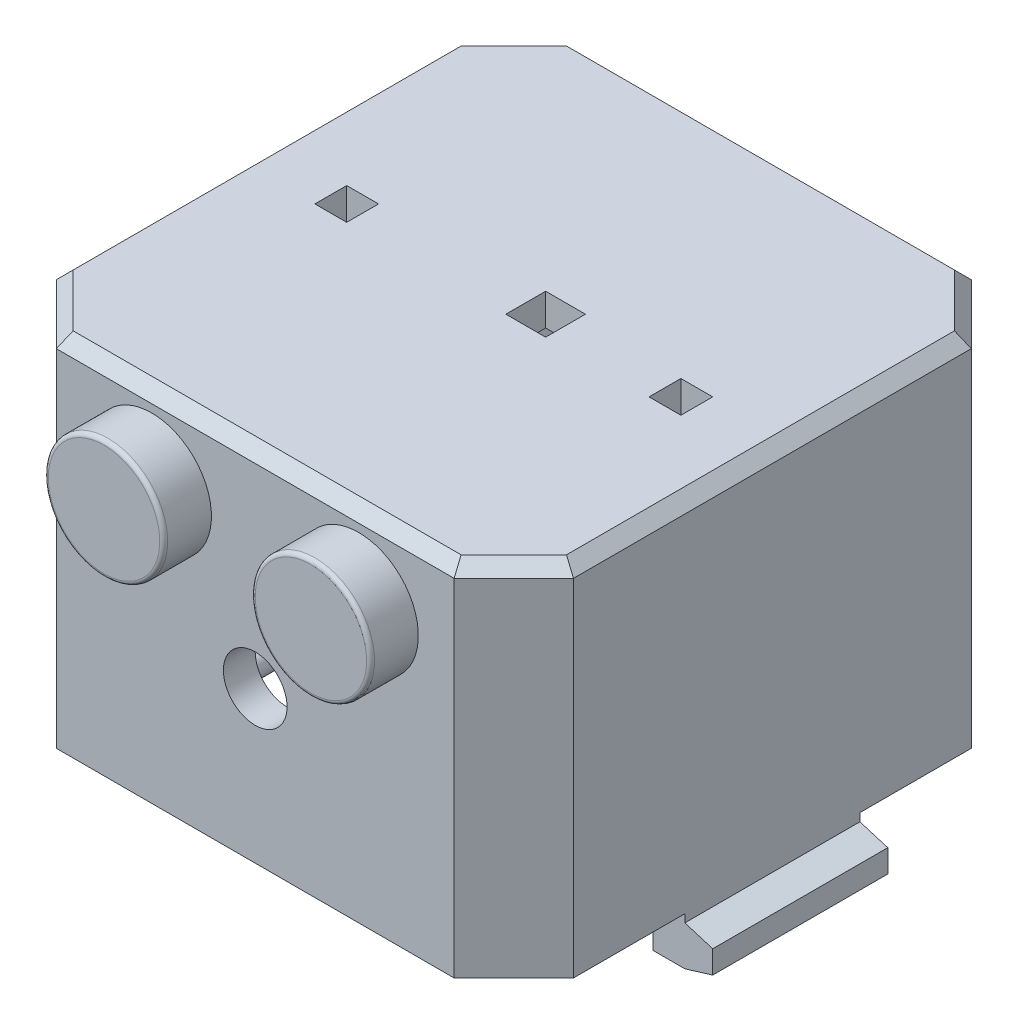
SolidWorks part; units mm, degrees
ref_plane "Alzado" through (0, 0, 0) normal (0, 0, 1) x (1, 0, 0)
ref_plane "Planta" through (0, 0, 0) normal (0, 1, 0) x (1, 0, 0)
ref_plane "Vista lateral" through (0, 0, 0) normal (1, 0, 0) x (0, 0, -1)
sketch "Croquis1" plane through (0, 0, 0) normal (0, 1, 0) x (1, 0, 0)
  line L1 (-25, -32.5) -> (25, -32.5)
  line L3 (-25, 32.5) -> (25, 32.5)
  line L5 (-25, -32.5) -> (25, 32.5) construction
  line L6 (-25, 32.5) -> (25, -32.5) construction
  line L10 (32.5, 25) -> (32.5, -25)
  line L11 (25, -32.5) -> (32.5, -25)
  line L12 (32.5, 25) -> (25, 32.5)
  line L13 (-32.5, 25) -> (-32.5, -25)
  line L14 (-32.5, -25) -> (-25, -32.5)
  line L15 (-32.5, 25) -> (-25, 32.5)
  point P0 (0, 0)
  point P10 (0, 32.5)
  dimension "D1" = 65
  dimension "D2" = 65
  dimension "D3" = 50
  dimension "D4" = 50
  dimension "D5" = 25
  dimension "D6" = 25
extrude "Saliente-Extruir1" add sketch "Croquis1" along normal blind 45
shell "Vaciado2" thickness 4 removed face at (0, 0, 0)
chamfer "Chaflán3" distance 1.5 angle 45 8 edges at (0, 45, -32.5) (32.5, 45, 0) (0, 45, 32.5) (-32.5, 45, 0) (-28.75, 45, 28.75) (28.75, 45, 28.75) (28.75, 45, -28.75) (-28.75, 45, -28.75)
sketch "Croquis2" plane through (0, 0, 32.5) normal (0, 0, 1) x (1, 0, 0)
  line L0 (0, 0) -> (0, 6.916) construction
  circle A0 centre (13, 35) radius 7.5
  circle A1 centre (-13, 35) radius 7.5
  dimension "D1" = 15
  dimension "D2" = 13
  dimension "D3" = 35
extrude "Saliente-Extruir2" add sketch "Croquis2" along normal blind 6
sketch "Croquis4" plane through (0, 0, 28.5) normal (0, 0, -1) x (-1, 0, 0)
  line L0 (0, 0) -> (0, 4.7403) construction
  line L1 (0, 0) -> (0, 6.916) construction
  circle A0 centre (-13, 35) radius 5
  circle A1 centre (13, 35) radius 5
  dimension "D1" = 10
extrude "Cortar-Extruir2" cut sketch "Croquis4" against normal blind 8
fillet "Redondeo1" radius 0.5 2 edges at (-20.5, 35, 38.5) (20.5, 35, 38.5)
sketch "Croquis5" plane through (0, 0, 32.5) normal (0, 0, 1) x (1, 0, 0)
  circle A0 centre (0, 19) radius 4
  dimension "D2" = 8
  dimension "D1" = 19
extrude "Cortar-Extruir3" cut sketch "Croquis5" against normal blind 10
sketch "Croquis13" plane through (0, 0, 36.5) normal (0, 0, -1) x (-1, 0, 0)
  circle A0 centre (-13, 35) radius 2.6
  circle A1 centre (13, 35) radius 2.6
  circle A2 centre (13, 35) radius 5
  circle A3 centre (-13, 35) radius 5
  dimension "D1" = 5.2
  dimension "D2" = 5.2
extrude "Saliente-Extruir8" add sketch "Croquis13" along normal blind 8
sketch "Croquis7" plane through (0, 0, 28.5) normal (0, 0, -1) x (-1, 0, 0)
  line L0 (23.3431, 0) -> (-23.3431, 0) construction
  line L1 (-14.08, 8) -> (-9.08, 8)
  line L2 (-14.08, 8) -> (-14.08, 13)
  line L3 (-14.08, 13) -> (-9.08, 13)
  line L4 (-9.08, 8) -> (-9.08, 13)
  line L5 (-14.08, 8) -> (-9.08, 13) construction
  line L6 (-14.08, 13) -> (-9.08, 8) construction
  line L8 (-14.08, 25.5) -> (-9.08, 25.5)
  line L9 (-14.08, 25.5) -> (-14.08, 30.5)
  line L10 (-14.08, 30.5) -> (-9.08, 30.5)
  line L11 (-9.08, 25.5) -> (-9.08, 30.5)
  line L12 (-14.08, 25.5) -> (-9.08, 30.5) construction
  line L13 (-14.08, 30.5) -> (-9.08, 25.5) construction
  line L14 (13.93, 13) -> (8.93, 8) construction
  line L15 (13.93, 8) -> (8.93, 13) construction
  line L16 (8.93, 8) -> (8.93, 13)
  line L17 (13.93, 13) -> (8.93, 13)
  line L18 (13.93, 8) -> (13.93, 13)
  line L19 (13.93, 8) -> (8.93, 8)
  line L20 (13.93, 30.5) -> (8.93, 25.5) construction
  line L21 (13.93, 25.5) -> (8.93, 30.5) construction
  line L22 (8.93, 25.5) -> (8.93, 30.5)
  line L23 (13.93, 30.5) -> (8.93, 30.5)
  line L24 (13.93, 25.5) -> (13.93, 30.5)
  line L25 (13.93, 25.5) -> (8.93, 25.5)
  point P0 (-11.58, 10.5)
  point P8 (-11.58, 28)
  point P13 (0, 0)
  point P15 (11.43, 10.5)
  point P16 (11.43, 28)
  point P20 (11.43, 10.5)
  point P25 (11.43, 28)
  point P26 (-11.58, 28)
  point P27 (11.43, 28)
  point P28 (11.43, 10.5)
  point P29 (-11.58, 10.5)
  dimension "D1" = 10.5
  dimension "D2" = 5
  dimension "D3" = 5
  dimension "D4" = 11.58
  dimension "D5" = 5
  dimension "D6" = 5
  dimension "D7" = 28
  dimension "D8" = 23.01
  dimension "D9" = 23.01
  dimension "D10" = 5
  dimension "D11" = 5
  dimension "D12" = 5
  dimension "D13" = 5
  dimension "D14" = 10.5
  dimension "D15" = 28
extrude "Saliente-Extruir3" add sketch "Croquis7" along normal blind 1
sketch "Croquis8" plane through (0, 0, 27.5) normal (0, 0, -1) x (-1, 0, 0)
  line L0 (0, 0) -> (0, 4.8013) construction
  line L1 (23.3431, 0) -> (-23.3431, 0) construction
  circle A0 centre (-11.505, 10.4893) radius 1.6
  circle A1 centre (-11.505, 27.9763) radius 1.6
  circle A2 centre (11.505, 10.4893) radius 1.6
  circle A3 centre (11.505, 27.9763) radius 1.6
  dimension "D1" = 3.2
  dimension "D2" = 3.2
  dimension "D5" = 3.2
  dimension "D3" = 23.01
  dimension "D4" = 23.01
sketch "Croquis12" plane through (0, 41, 0) normal (0, -1, 0) x (1, 0, 0)
  line L0 (0, 0) -> (-5.199, 0) construction
  line L1 (-21.9, -8.93) -> (21.9, -8.93) construction
  line L2 (-21.9, -8.93) -> (-21.9, 8.93) construction
  line L3 (-21.9, 8.93) -> (21.9, 8.93) construction
  line L4 (21.9, -8.93) -> (21.9, 8.93) construction
  line L5 (-21.9, -8.93) -> (21.9, 8.93) construction
  line L6 (-21.9, 8.93) -> (21.9, -8.93) construction
  line L7 (0, 0) -> (0, 4.1573) construction
  circle A0 centre (-20.65, 7.68) radius 0.8
  circle A1 centre (-20.65, 7.68) radius 1.15
  circle A2 centre (-20.65, -7.68) radius 1.15
  circle A3 centre (-20.65, -7.68) radius 0.8
  circle A4 centre (20.65, 7.68) radius 1.15
  circle A5 centre (20.65, 7.68) radius 0.8
  circle A6 centre (20.65, -7.68) radius 1.15
  circle A7 centre (20.65, -7.68) radius 0.8
  point P0 (0, 0)
  dimension "D6" = 1.6
  dimension "D4" = 2.3
  dimension "D1" = 43.8
  dimension "D2" = 17.86
  dimension "D3" = 1.25
  dimension "D7" = 1.25
extrude "Saliente-Extruir7" add sketch "Croquis12" along normal blind 6
sketch "Croquis14" plane through (0, 41, 0) normal (0, -1, 0) x (1, 0, 0)
  line L1 (-22.15, 6.43) -> (-19.15, 6.43)
  line L2 (-22.15, 6.43) -> (-22.15, 8.93)
  line L3 (-22.15, 8.93) -> (-19.15, 8.93)
  line L4 (-19.15, 6.43) -> (-19.15, 8.93)
  line L5 (-22.15, 6.43) -> (-19.15, 8.93) construction
  line L6 (-22.15, 8.93) -> (-19.15, 6.43) construction
  line L7 (-22.15, -8.93) -> (-19.15, -8.93)
  line L8 (-22.15, -8.93) -> (-22.15, -6.43)
  line L9 (-22.15, -6.43) -> (-19.15, -6.43)
  line L10 (-19.15, -8.93) -> (-19.15, -6.43)
  line L11 (-22.15, -8.93) -> (-19.15, -6.43) construction
  line L12 (-22.15, -6.43) -> (-19.15, -8.93) construction
  line L13 (19.15, 6.43) -> (22.15, 6.43)
  line L14 (19.15, 6.43) -> (19.15, 8.93)
  line L15 (19.15, 8.93) -> (22.15, 8.93)
  line L16 (22.15, 6.43) -> (22.15, 8.93)
  line L17 (19.15, 6.43) -> (22.15, 8.93) construction
  line L18 (19.15, 8.93) -> (22.15, 6.43) construction
  line L19 (19.15, -8.93) -> (22.15, -8.93)
  line L20 (19.15, -8.93) -> (19.15, -6.43)
  line L21 (19.15, -6.43) -> (22.15, -6.43)
  line L22 (22.15, -8.93) -> (22.15, -6.43)
  line L23 (19.15, -8.93) -> (22.15, -6.43) construction
  line L24 (19.15, -6.43) -> (22.15, -8.93) construction
  point P0 (-20.65, 7.68)
  point P6 (-20.65, -7.68)
  point P12 (20.65, 7.68)
  point P18 (20.65, -7.68)
  dimension "D1" = 3
  dimension "D2" = 2.5
  dimension "D3" = 3
  dimension "D4" = 2.5
  dimension "D5" = 3
  dimension "D6" = 2.5
  dimension "D7" = 3
  dimension "D8" = 2.5
extrude "Saliente-Extruir9" add sketch "Croquis14" along normal blind 5
sketch "Croquis15" plane through (-32.5, 0, 0) normal (-1, 0, 0) x (0, 0, 1)
  line L1 (-6, 40.5) -> (6, 40.5)
  line L2 (-6, 40.5) -> (-6, 32.5)
  line L3 (-6, 32.5) -> (6, 32.5)
  line L4 (6, 40.5) -> (6, 32.5)
  dimension "D1" = 8
  dimension "D2" = 12
  dimension "D3" = 3
  dimension "D4" = 19
extrude "Cortar-Extruir6" cut sketch "Croquis15" against normal blind 7
sketch "Croquis16" plane through (0, 0, -28.5) normal (0, 0, 1) x (1, 0, 0)
  line L2 (18.95, 6.05) -> (6.55, 6.05)
  line L3 (18.95, 6.05) -> (18.95, 18.45)
  line L4 (18.95, 18.45) -> (6.55, 18.45)
  line L5 (6.55, 6.05) -> (6.55, 18.45)
  line L6 (5.5, 5) -> (20, 5)
  line L7 (5.5, 5) -> (5.5, 19.5)
  line L8 (5.5, 19.5) -> (20, 19.5)
  line L9 (20, 5) -> (20, 19.5)
  line L10 (5.5, 5) -> (20, 19.5) construction
  line L11 (5.5, 19.5) -> (20, 5) construction
  line L12 (18.95, 6.05) -> (6.55, 18.45) construction
  line L13 (18.95, 18.45) -> (6.55, 6.05) construction
  point P0 (12.75, 12.25)
  point P4 (12.75, 12.25)
  dimension "D1" = 12.4
  dimension "D2" = 12.4
  dimension "D3" = 5
  dimension "D4" = 5
  dimension "D5" = 14.5
  dimension "D6" = 14.5
extrude "Saliente-Extruir10" add sketch "Croquis16" along normal blind 3
sketch "Croquis17" plane through (0, 0, -28.5) normal (0, 0, 1) x (1, 0, 0)
  circle A0 centre (12.75, 12.25) radius 5.5
  point P4 (12.75, 12.25)
  dimension "D1" = 11
extrude "Cortar-Extruir7" cut sketch "Croquis17" against normal through all
sketch "Croquis18" plane through (0, 0, 0) normal (0, -1, 0) x (1, 0, 0)
  line L1 (-32.5, 11) -> (-28.5, 11)
  line L2 (-32.5, 11) -> (-32.5, -11)
  line L3 (-32.5, -11) -> (-28.5, -11)
  line L4 (-28.5, 11) -> (-28.5, -11)
  line L5 (-32.5, -25) -> (-32.5, 25) construction
  line L6 (0, 0) -> (0, 8.739) construction
  line L7 (28.5, 11) -> (28.5, -11)
  line L8 (32.5, -11) -> (28.5, -11)
  line L9 (32.5, 11) -> (32.5, -11)
  line L10 (32.5, 11) -> (28.5, 11)
  point P4 (-28.5, 0)
  dimension "D1" = 4
  dimension "D2" = 22
extrude "Saliente-Extruir11" add sketch "Croquis18" along normal blind 6
sketch "Croquis19" plane through (0, 0, 11) normal (0, 0, 1) x (1, 0, 0)
  line L0 (-32.5, -3.5) -> (-34.5, -3.5) construction
  line L1 (36, -2.0667) -> (36, -4.9333)
  line L2 (-34.5, -2.0568) -> (-32.5, -1)
  line L3 (-32.5, -6) -> (-32.5, 0)
  line L4 (-32.5, -6) -> (-32.5, -1)
  line L5 (-32.5, -6) -> (-34.5, -4.9432)
  line L6 (0, 0) -> (0, 6.3616) construction
  line L7 (-25, 0) -> (25, 0) construction
  line L8 (32.5, -3.5) -> (36, -3.5) construction
  line L9 (32.5, -6) -> (36, -4.9333)
  line L10 (32.5, -6) -> (32.5, -1)
  line L11 (32.5, -6) -> (32.5, 0)
  line L12 (36, -2.0667) -> (32.5, -1)
  line L14 (-34.5, -2.0568) -> (-34.5, -4.9432)
  line M6 (-32.5, 0) -> (-32.5, -6)
  dimension "D1" = 2
  dimension "D2" = 3.5
extrude "Saliente-Extruir13" add sketch "Croquis19" against normal blind 22 contours L5 L2 M6 | L12 L10 L9 region at (34.0918, -3.5, 11) region at (-33.4107, -3.5, 11)
sketch "Croquis20" plane through (0, 45, 0) normal (0, 1, 0) x (1, 0, 0)
  line L1 (6.0029, -2) -> (1.0029, -2)
  line L2 (6.0029, -2) -> (6.0029, 3)
  line L3 (6.0029, 3) -> (1.0029, 3)
  line L4 (1.0029, -2) -> (1.0029, 3)
  dimension "D1" = 5
  dimension "D2" = 5
  dimension "D3" = 2
extrude "Cortar-Extruir8" cut sketch "Croquis20" against normal blind 10
sketch "Croquis10" plane through (0, 45, 0) normal (0, 1, 0) x (1, 0, 0)
  line L0 (-31, 24.3787) -> (-31, -24.3787) construction
  line L1 (-31, -4) -> (-11, -4) construction
  line L2 (-31, -4) -> (-31, 4) construction
  line L3 (-31, 4) -> (-11, 4) construction
  line L4 (-11, -4) -> (-11, 4) construction
  line L5 (-31, -4) -> (-11, 4) construction
  line L6 (-31, 4) -> (-11, -4) construction
  line L7 (0, 0) -> (0, 7.307) construction
  line L8 (31, 4) -> (11, -4) construction
  line L9 (31, -4) -> (11, 4) construction
  line L10 (11, -4) -> (11, 4) construction
  line L11 (31, 4) -> (11, 4) construction
  line L12 (31, -4) -> (31, 4) construction
  line L13 (31, -4) -> (11, -4) construction
  line L15 (-23, -2) -> (-19, -2)
  line L16 (-23, -2) -> (-23, 2)
  line L17 (-23, 2) -> (-19, 2)
  line L18 (-19, -2) -> (-19, 2)
  line L19 (-23, -2) -> (-19, 2) construction
  line L20 (-23, 2) -> (-19, -2) construction
  line L21 (19, -2) -> (23, -2)
  line L22 (19, -2) -> (19, 2)
  line L23 (19, 2) -> (23, 2)
  line L24 (23, -2) -> (23, 2)
  line L25 (19, -2) -> (23, 2) construction
  line L26 (19, 2) -> (23, -2) construction
  circle A0 centre (-21, 0) radius 2 construction
  circle A1 centre (21, 0) radius 2 construction
  point P0 (-21, 0)
  point P14 (21, 0)
  dimension "D3" = 4
  dimension "D4" = 4
  dimension "D1" = 20
  dimension "D2" = 8
extrude "Cortar-Extruir10" cut sketch "Croquis10" against normal through all
sketch "Croquis21" plane through (0, 36, 0) normal (0, -1, 0) x (1, 0, 0)
  circle A0 centre (-20.65, 7.68) radius 0.8
  circle A1 centre (20.65, 7.68) radius 0.8
  circle A2 centre (20.65, -7.68) radius 0.8
  circle A3 centre (-20.65, -7.68) radius 0.8
extrude "Cortar-Extruir11" cut sketch "Croquis21" against normal blind 5
extrude "Saliente-Extruir14" add sketch "Croquis8" along normal blind 8
